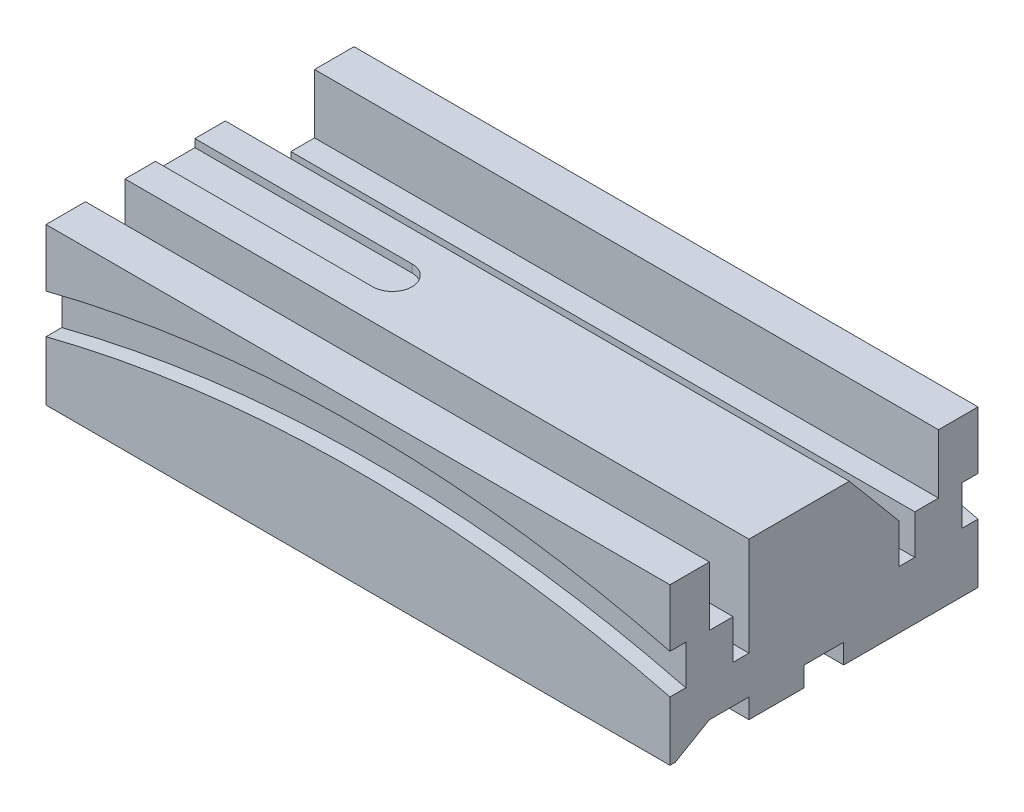
SolidWorks part; units mm, degrees
ref_plane "Front Plane" through (0, 0, 0) normal (0, 0, 1) x (1, 0, 0)
ref_plane "Top Plane" through (0, 0, 0) normal (0, 1, 0) x (1, 0, 0)
ref_plane "Right Plane" through (0, 0, 0) normal (1, 0, 0) x (0, 0, -1)
sketch "Sketch1" plane through (0, 0, 0) normal (0, 1, 0) x (1, 0, 0)
  line L1 (-100.33, -49.53) -> (100.33, -49.53)
  line L2 (-100.33, -49.53) -> (-100.33, 49.53)
  line L3 (-100.33, 49.53) -> (100.33, 49.53)
  line L4 (100.33, -49.53) -> (100.33, 49.53)
  line L5 (-100.33, -49.53) -> (100.33, 49.53) construction
  line L6 (-100.33, 49.53) -> (100.33, -49.53) construction
  point P0 (0, 0)
  dimension "D1" = 200.66
  dimension "D2" = 99.06
extrude "Boss-Extrude1" add sketch "Sketch1" against normal blind 50.292
sketch "Sketch2" plane through (-100.33, 0, 0) normal (-1, 0, 0) x (0, 0, 1)
  line L0 (-49.53, 0) -> (49.53, 0) construction
  line L1 (-36.83, 0) -> (-24.13, 0)
  line L2 (-36.83, 0) -> (-36.83, -19.05)
  line L3 (-36.83, -19.05) -> (-24.13, -19.05)
  line L4 (-24.13, 0) -> (-24.13, -19.05)
  line L5 (-49.53, -50.292) -> (-49.53, 0) construction
  dimension "D1" = 19.05
  dimension "D2" = 12.7
  dimension "D3" = 12.7
extrude "Cut-Extrude1" cut sketch "Sketch2" against normal through all
sketch "Sketch3" plane through (-100.33, 0, 0) normal (-1, 0, 0) x (0, 0, 1)
  line L0 (-36.83, -19.05) -> (-24.13, -19.05) construction
  line L1 (-29.21, -19.05) -> (-24.13, -19.05)
  line L2 (-29.21, -19.05) -> (-29.21, -31.75)
  line L3 (-29.21, -31.75) -> (-24.13, -31.75)
  line L4 (-24.13, -19.05) -> (-24.13, -31.75)
  line L5 (-24.13, -19.05) -> (-24.13, 0) construction
  line L6 (-36.83, 0) -> (-36.83, -19.05) construction
  dimension "D1" = 12.7
  dimension "D2" = 7.62
extrude "Cut-Extrude2" cut sketch "Sketch3" against normal through all
sketch "Sketch4" plane through (-100.33, 0, 0) normal (-1, 0, 0) x (0, 0, 1)
  line L0 (-1033.02, -19.05) -> (48966.98, -19.05) construction
  line L1 (-36.83, -19.05) -> (-29.21, -19.05) construction
  line L2 (-24.13, -19.05) -> (-8.1452, 0)
  line L3 (-24.13, 0) -> (49.53, 0) construction
  line L4 (-8.1452, 0) -> (-24.13, 0)
  line L5 (-24.13, 0) -> (-24.13, -19.05)
  line L6 (-24.13, -31.75) -> (-24.13, 0) construction
  point P5 (-33.02, -19.05)
  dimension "D1" = 40
extrude "Cut-Extrude3" cut sketch "Sketch4" against normal through all
mirror "Mirror1" about plane through (0, 0, 0) normal (0, 0, 1) of "Cut-Extrude3", "Cut-Extrude2", "Cut-Extrude1"
sketch "Sketch5" plane through (100.33, 0, 0) normal (1, 0, 0) x (0, 0, -1)
  line L0 (-24.13, -19.05) -> (-8.1452, 0)
  line L1 (-8.1452, 0) -> (-24.13, 0)
  line L2 (-24.13, 0) -> (-24.13, -19.05)
extrude "Boss-Extrude2" add sketch "Sketch5" against normal up to surface (200.66 mm away) up to face at (-100.33, -18.9936, 0)
sketch "Sketch6" plane through (100.33, 0, 0) normal (1, 0, 0) x (0, 0, -1)
  line L0 (0, -1000) -> (0, 49000) construction
  line L1 (-49.53, -50.292) -> (49.53, -50.292) construction
  line L2 (-6.35, -50.292) -> (6.35, -50.292)
  line L3 (-6.35, -50.292) -> (-6.35, -43.942)
  line L4 (-6.35, -43.942) -> (6.35, -43.942)
  line L5 (6.35, -50.292) -> (6.35, -43.942)
  dimension "D1" = 12.7
  dimension "D2" = 6.35
extrude "Cut-Extrude4" cut sketch "Sketch6" against normal through all
sketch "Sketch7" plane through (-100.33, 0, 0) normal (-1, 0, 0) x (0, 0, 1)
  line L0 (24.13, -50.292) -> (24.13, -43.942)
  line L1 (6.35, -50.292) -> (49.53, -50.292) construction
  line L2 (24.13, -43.942) -> (36.83, -43.942)
  line L3 (36.83, -43.942) -> (47.8285, -50.292)
  line L4 (47.8285, -50.292) -> (24.13, -50.292)
  line L5 (-6.35, -43.942) -> (6.35, -43.942) construction
  line L6 (24.13, -31.75) -> (24.13, 0) construction
  dimension "D1" = 150
extrude "Cut-Extrude5" cut sketch "Sketch7" against normal through all
sketch "Sketch8" plane through (0, 0, 49.53) normal (0, 0, 1) x (1, 0, 0)
  line L0 (-100.33, -50.292) -> (-100.33, 0) construction
  line L1 (100.33, -50.292) -> (100.33, 0) construction
  line L2 (-100.33, -50.292) -> (100.33, -50.292) construction
  line L3 (-100.33, -18.542) -> (-100.33, -31.242)
  line L4 (100.33, -18.542) -> (100.33, -31.242)
  arc A0 (-100.33, -18.542) -> (100.33, -18.542) centre (0, -412.3628) cw
  arc A1 (-100.33, -31.242) -> (100.33, -31.242) centre (0, -425.0628) cw
  dimension "D1" = 31.75
  dimension "D2" = 406.4
  dimension "D4" = 12.7
  dimension "D3" = 2
extrude "Cut-Extrude6" cut sketch "Sketch8" against normal blind 5.08
mirror "Mirror2" about plane through (0, 0, 0) normal (0, 0, 1) of "Cut-Extrude6"
sketch "Sketch9" plane through (0, 0, -49.53) normal (0, 0, -1) x (-1, 0, 0)
  line L0 (100.33, -18.542) -> (100.33, -31.242) construction
  line L1 (100.33, -18.542) -> (100.33, -31.242)
  arc A1 (100.33, -31.242) -> (-100.33, -31.242) centre (0, -425.0628) ccw construction
  arc A4 (100.33, -31.242) -> (0, -18.6628) centre (0, -425.0628) ccw
  arc A5 (100.33, -18.542) -> (-100.33, -18.542) centre (0, -412.3628) ccw construction
  arc A6 (100.33, -18.542) -> (0, -5.9628) centre (0, -412.3628) ccw
  arc A7 (0, -5.9628) -> (0, -18.6628) centre (0, -12.3128) cw
  dimension "D1" = 6.35
extrude "Boss-Extrude3" add sketch "Sketch9" against normal up to surface (5.08 mm away) up to face at (0, -18.6024, -44.45)
sketch "Sketch13" plane through (0, 0, 0) normal (0, 1, 0) x (1, 0, 0)
  line L0 (-100.33, 8.1452) -> (-100.33, -24.13) construction
  line L1 (-176.53, -1.6424) -> (-24.13, -1.6424)
  line L2 (-176.53, -1.6424) -> (-176.53, -14.3424)
  line L3 (-176.53, -14.3424) -> (-24.13, -14.3424)
  line L4 (-24.13, -1.6424) -> (-24.13, -14.3424)
  line L5 (-176.53, -1.6424) -> (-24.13, -14.3424) construction
  line L6 (-176.53, -14.3424) -> (-24.13, -1.6424) construction
  point P0 (-100.33, -7.9924)
  dimension "D1" = 12.7
  dimension "D2" = 76.2
extrude "Cut-Extrude7" cut sketch "Sketch13" against normal blind 2.54
fillet "Fillet1" radius 6.35 2 edges at (-24.13, -1.27, 14.3424) (-24.13, -1.27, 1.6424)
